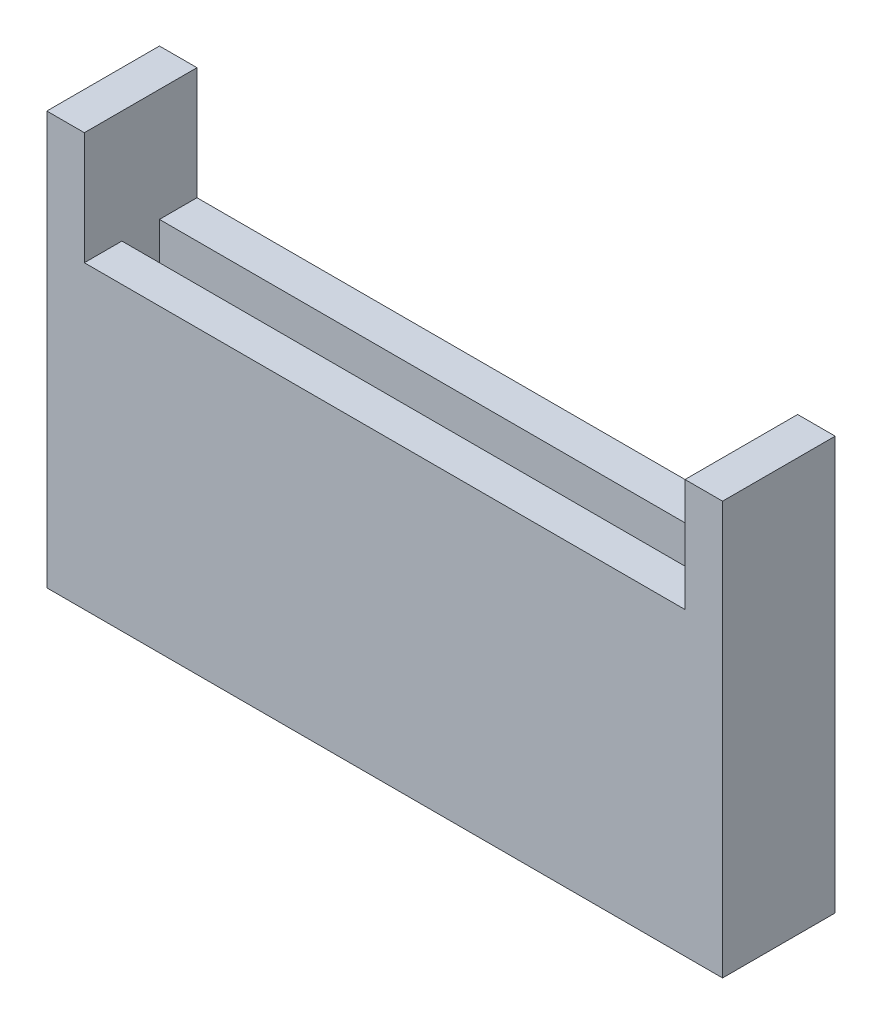
SolidWorks part; units mm, degrees
ref_plane "Front Plane" through (0, 0, 0) normal (0, 0, 1) x (1, 0, 0)
ref_plane "Top Plane" through (0, 0, 0) normal (0, 1, 0) x (1, 0, 0)
ref_plane "Right Plane" through (0, 0, 0) normal (1, 0, 0) x (0, 0, -1)
sketch "Sketch1" plane through (0, 0, 0) normal (0, 1, 0) x (1, 0, 0)
  line L0 (0, 0) -> (-18, 0)
  line L5 (-18, 0) -> (-18, 3)
  line L6 (-18, 3) -> (0, 3)
  line L7 (0, 3) -> (0, 0)
  line L8 (-17, 3) -> (-17, 0)
  line L9 (-1, 3) -> (-1, 0)
  line L10 (-17, 2) -> (-2, 2)
  line L11 (-17, 1) -> (-1, 1)
  line L12 (-2, 2) -> (-2, 3)
  point P0 (0, 0)
  dimension "D1" = 3
  dimension "D2" = 18
  dimension "D3" = 1
  dimension "D4" = 1
  dimension "D5" = 1
  dimension "D6" = 1
  dimension "D7" = 1
extrude "Boss-Extrude1" add sketch "Sketch1" along normal blind 11 contours L6 L9 L0 L7 | L8 L6 L5 L0 region at (-0.5, 0, -1.5) region at (-17.5, 0, -1.5)
extrude "Boss-Extrude2" add sketch "Sketch1<7>" along normal blind 8 contours L10 L12 L6 L8 | L11 L8 L0 L9 region at (-9, 0, -0.5) region at (-9.5, 0, -2.5)
sketch "Sketch1<7>" plane through (0, 0, 0) normal (0, 1, 0) x (1, 0, 0) same geometry as "Sketch1"
extrude "Boss-Extrude3" add sketch "Sketch1<8>" along normal blind 1 contours L12 L10 L8 L11 L9 L6 region at (-8.5588, 0, -1.5588)
sketch "Sketch1<8>" plane through (0, 0, 0) normal (0, 1, 0) x (1, 0, 0) same geometry as "Sketch1"
